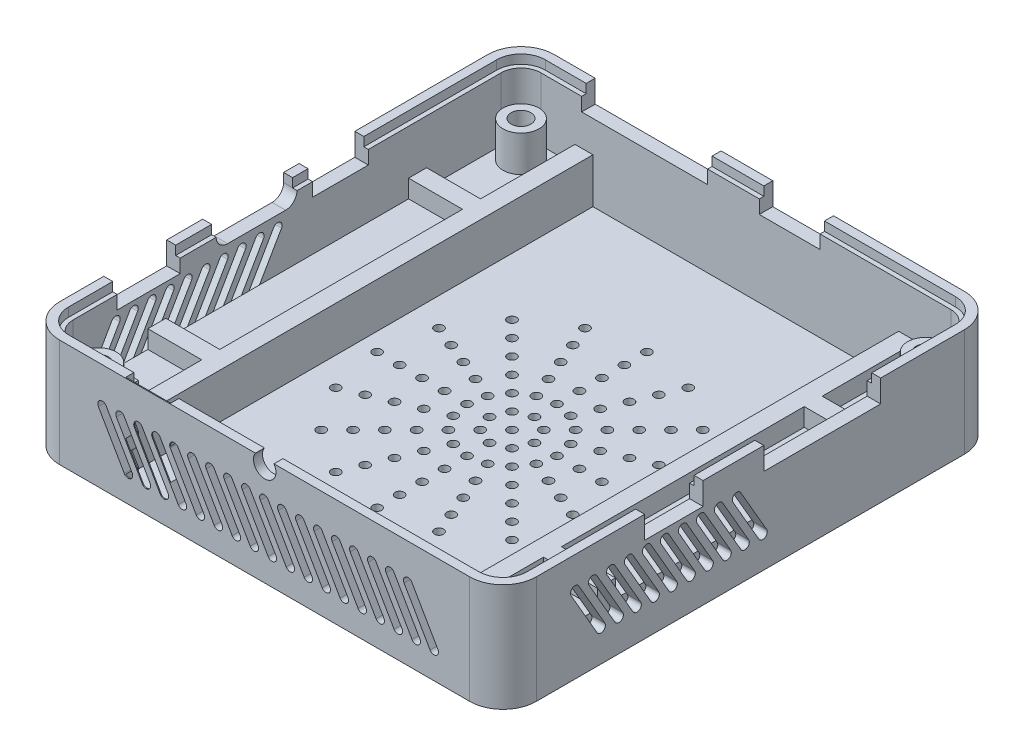
SolidWorks part; units mm, degrees
ref_plane "Front Plane" through (0, 0, 0) normal (0, 0, 1) x (1, 0, 0)
ref_plane "Top Plane" through (0, 0, 0) normal (0, 1, 0) x (1, 0, 0)
ref_plane "Right Plane" through (0, 0, 0) normal (1, 0, 0) x (0, 0, -1)
sketch "Sketch1" plane through (0, 0, 0) normal (0, 1, 0) x (1, 0, 0)
  line L5 (-25.5, 23.8) -> (-25.5, -23.8)
  line L6 (-22.8, 26) -> (22.8, 26)
  line L18 (-25, 23.8) -> (-25, -23.8)
  line L19 (-22.8, -26) -> (22.8, -26)
  line L20 (25, 23.8) -> (25, -23.8)
  line L21 (-25, 26) -> (25, -26) construction
  line L22 (-25, -26) -> (25, 26) construction
  line L23 (-22.8, -26.5) -> (22.8, -26.5)
  line L24 (25.5, 23.8) -> (25.5, -23.8)
  line L25 (-22.8, 26.5) -> (22.8, 26.5)
  line L26 (-26.5, 23.8) -> (-26.5, -23.8)
  line L27 (-22.8, -27.5) -> (22.8, -27.5)
  line L28 (26.5, 23.8) -> (26.5, -23.8)
  line L29 (-22.8, 27.5) -> (22.8, 27.5)
  line L30 (-19, 13.5) -> (-19, -13.5)
  line L31 (-19, 26) -> (-17, 26)
  line L32 (-19, 26) -> (-19, 15.5)
  line L33 (-19, -26) -> (-17, -26)
  line L34 (-17, 26) -> (-17, -26)
  line L35 (17, -26) -> (19, -26)
  line L36 (17, -26) -> (17, 26)
  line L37 (17, 26) -> (19, 26)
  line L38 (19, -26) -> (19, -15.5)
  line L39 (-25, 15.5) -> (-19, 15.5)
  line L40 (-25, 15.5) -> (-25, 13.5)
  line L41 (-25, 13.5) -> (-19, 13.5)
  line L43 (-25, -13.5) -> (-19, -13.5)
  line L44 (-25, -13.5) -> (-25, -15.5)
  line L45 (-25, -15.5) -> (-19, -15.5)
  line L47 (19, 15.5) -> (25, 15.5)
  line L48 (17, 15.5) -> (17, 13.5)
  line L49 (19, 13.5) -> (25, 13.5)
  line L50 (25, 15.5) -> (25, 13.5)
  line L51 (19, -13.5) -> (25, -13.5)
  line L52 (17, -13.5) -> (17, -15.5)
  line L53 (19, -15.5) -> (25, -15.5)
  line L54 (25, -13.5) -> (25, -15.5)
  line L55 (19, 15.5) -> (19, 26)
  line L56 (19, -13.5) -> (19, 13.5)
  line L57 (-19, -15.5) -> (-19, -26)
  circle A20 centre (-22.5, 23.5) radius 1.1
  circle A21 centre (22.5, 23.5) radius 1.1
  circle A22 centre (-22.5, -23.5) radius 1.1
  circle A23 centre (22.5, -23.5) radius 1.1
  circle A24 centre (-22.5, 23.5) radius 2
  circle A25 centre (22.5, 23.5) radius 2
  circle A26 centre (22.5, -23.5) radius 2
  circle A27 centre (-22.5, -23.5) radius 2
  arc A28 (-22.8, -26) -> (-25, -23.8) centre (-22.8, -23.8) cw
  arc A29 (25, -23.8) -> (22.8, -26) centre (22.8, -23.8) cw
  arc A30 (25, 23.8) -> (22.8, 26) centre (22.8, 23.8) ccw
  arc A31 (-22.8, 26) -> (-25, 23.8) centre (-22.8, 23.8) ccw
  arc A32 (-22.8, -26.5) -> (-25.5, -23.8) centre (-22.8, -23.8) cw
  arc A33 (25.5, -23.8) -> (22.8, -26.5) centre (22.8, -23.8) cw
  arc A34 (25.5, 23.8) -> (22.8, 26.5) centre (22.8, 23.8) ccw
  arc A35 (-22.8, 26.5) -> (-25.5, 23.8) centre (-22.8, 23.8) ccw
  arc A36 (-22.8, -27.5) -> (-26.5, -23.8) centre (-22.8, -23.8) cw
  arc A37 (26.5, -23.8) -> (22.8, -27.5) centre (22.8, -23.8) cw
  arc A38 (26.5, 23.8) -> (22.8, 27.5) centre (22.8, 23.8) ccw
  arc A39 (-22.8, 27.5) -> (-26.5, 23.8) centre (-22.8, 23.8) ccw
  point P0 (0, 0)
  dimension "D3" = 2.2
  dimension "D6" = 2.2
  dimension "D7" = 2.5
  dimension "D8" = 2.5
  dimension "D9" = 2.5
  dimension "D10" = 2.5
  dimension "D11" = 2.5
  dimension "D12" = 2.5
  dimension "D13" = 2.5
  dimension "D14" = 2.5
  dimension "D15" = 4
  dimension "D16" = 4
  dimension "D17" = 4
  dimension "D18" = 4
  dimension "D19" = 2.2
  dimension "D20" = 0.5
  dimension "D4" = 2.2
  dimension "D5" = 2.2
  dimension "D1" = 52
  dimension "D2" = 50
  dimension "D22" = 53
  dimension "D23" = 36
  dimension "D24" = 2
  dimension "D25" = 2
  dimension "D26" = 6
  dimension "D27" = 6
  dimension "D28" = 2
  dimension "D29" = 8
  dimension "D30" = 2
  dimension "D31" = 8
  dimension "D32" = 2
  dimension "D33" = 8
  dimension "D34" = 2
  dimension "D35" = 8
  dimension "D21" = 1.5
extrude "Boss-Extrude1" add sketch "Sketch1" along normal blind 12 contours L29 A39 L26 A36 L27 A37 L28 A38 A35 L25 A34 L24 A33 L23 A32 L5 region at (-24.8762, 0, -25.8762)
extrude "Boss-Extrude2" add sketch "Sketch1<10>" along normal blind 11 contours L25 A35 L5 A32 L23 A33 L24 A34 A31 L6 A30 L20 A29 L19 A28 L18 region at (-24.6572, 0, -25.6572)
sketch "Sketch1<10>" plane through (0, 0, 0) normal (0, 1, 0) x (1, 0, 0) same geometry as "Sketch1"
extrude "Boss-Extrude3" add sketch "Sketch1<11>" along normal blind 8 separate body contours A24 A20 | A27 A22 | A26 A23 | A25 A21 region at (-24.4434, 0, -23.5) region at (20.5566, 0, -23.5) region at (20.5566, 0, 23.5) region at (-24.4434, 0, 23.5)
sketch "Sketch1<11>" plane through (0, 0, 0) normal (0, 1, 0) x (1, 0, 0) same geometry as "Sketch1"
extrude "Boss-Extrude4" add sketch "Sketch1<12>" along normal blind 4 contours L18 L43 L30 L41 | L6 A31 L18 L39 L32 A24 | L19 L36 L6 L34 | A28 L19 L57 L45 L18 A27 | A29 L20 L53 L38 L19 A26 | L56 L51 L20 L49 | L20 A30 L6 L55 L47 A25 region at (-21.82, 0, -19.9503) region at (0, 0, 0) region at (-22, 0, 0) region at (21.82, 0, -19.9503) region at (-21.82, 0, 19.9503) region at (21.82, 0, 19.9503) region at (22, 0, 0)
sketch "Sketch1<12>" plane through (0, 0, 0) normal (0, 1, 0) x (1, 0, 0) same geometry as "Sketch1"
extrude "Boss-Extrude5" add sketch "Sketch1<13>" along normal blind 6 contours L45 L57 L19 L34 L6 L32 L39 L18 L41 L30 L43 | L51 L56 L49 L20 L47 L55 L6 L36 L19 L38 L53 region at (-18.75, 0, 0) region at (18.75, 0, 0)
sketch "Sketch1<13>" plane through (0, 0, 0) normal (0, 1, 0) x (1, 0, 0) same geometry as "Sketch1"
sketch "Sketch2" plane through (0, 4, 0) normal (0, 1, 0) x (1, 0, 0)
  line L1 (-17, 26) -> (17, 26)
  line L2 (-17, 26) -> (-17, -26)
  line L3 (-17, -26) -> (17, -26)
  line L4 (17, 26) -> (17, -26)
  line L5 (-17, 26) -> (17, -26) construction
  line L6 (-17, -26) -> (17, 26) construction
  point P0 (0, 0)
extrude "Cut-Extrude1" cut sketch "Sketch2" against normal blind 3
sketch "Sketch3" plane through (0, 0, 0) normal (0, -1, 0) x (1, 0, 0)
  circle A0 centre (-22.5, 23.5) radius 2
  circle A1 centre (22.5, 23.5) radius 2
  circle A2 centre (-22.5, -23.5) radius 2
  circle A3 centre (22.5, -23.5) radius 2
  circle A4 centre (0, 12.5) radius 0.5
  circle A5 centre (4.7835, 11.5485) radius 0.5
  circle A6 centre (8.8388, 8.8388) radius 0.5
  circle A7 centre (11.5485, 4.7835) radius 0.5
  circle A8 centre (12.5, 0) radius 0.5
  circle A9 centre (11.5485, -4.7835) radius 0.5
  circle A10 centre (8.8388, -8.8388) radius 0.5
  circle A11 centre (4.7835, -11.5485) radius 0.5
  circle A12 centre (0, -12.5) radius 0.5
  circle A13 centre (-4.7835, -11.5485) radius 0.5
  circle A14 centre (-8.8388, -8.8388) radius 0.5
  circle A15 centre (-11.5485, -4.7835) radius 0.5
  circle A16 centre (-12.5, 0) radius 0.5
  circle A17 centre (-11.5485, 4.7835) radius 0.5
  circle A18 centre (-8.8388, 8.8388) radius 0.5
  circle A19 centre (-4.7835, 11.5485) radius 0.5
  circle A20 centre (0, 10) radius 0.5
  circle A21 centre (0, 7.5) radius 0.5
  circle A22 centre (0, 5) radius 0.5
  circle A23 centre (0, 2.5) radius 0.5
  circle A24 centre (0, 0) radius 0.5
  circle A25 centre (3.8268, 9.2388) radius 0.5
  circle A26 centre (7.0711, 7.0711) radius 0.5
  circle A27 centre (9.2388, 3.8268) radius 0.5
  circle A28 centre (10, 0) radius 0.5
  circle A29 centre (9.2388, -3.8268) radius 0.5
  circle A30 centre (7.0711, -7.0711) radius 0.5
  circle A31 centre (3.8268, -9.2388) radius 0.5
  circle A32 centre (0, -10) radius 0.5
  circle A33 centre (-3.8268, -9.2388) radius 0.5
  circle A34 centre (-7.0711, -7.0711) radius 0.5
  circle A35 centre (-9.2388, -3.8268) radius 0.5
  circle A36 centre (-10, 0) radius 0.5
  circle A37 centre (-9.2388, 3.8268) radius 0.5
  circle A38 centre (-7.0711, 7.0711) radius 0.5
  circle A39 centre (-3.8268, 9.2388) radius 0.5
  circle A40 centre (2.8701, 6.9291) radius 0.5
  circle A41 centre (5.3033, 5.3033) radius 0.5
  circle A42 centre (6.9291, 2.8701) radius 0.5
  circle A43 centre (7.5, 0) radius 0.5
  circle A44 centre (6.9291, -2.8701) radius 0.5
  circle A45 centre (5.3033, -5.3033) radius 0.5
  circle A46 centre (2.8701, -6.9291) radius 0.5
  circle A47 centre (0, -7.5) radius 0.5
  circle A48 centre (-2.8701, -6.9291) radius 0.5
  circle A49 centre (-5.3033, -5.3033) radius 0.5
  circle A50 centre (-6.9291, -2.8701) radius 0.5
  circle A51 centre (-7.5, 0) radius 0.5
  circle A52 centre (-6.9291, 2.8701) radius 0.5
  circle A53 centre (-5.3033, 5.3033) radius 0.5
  circle A54 centre (-2.8701, 6.9291) radius 0.5
  circle A55 centre (1.9134, 4.6194) radius 0.5
  circle A56 centre (3.5355, 3.5355) radius 0.5
  circle A57 centre (4.6194, 1.9134) radius 0.5
  circle A58 centre (5, 0) radius 0.5
  circle A59 centre (4.6194, -1.9134) radius 0.5
  circle A60 centre (3.5355, -3.5355) radius 0.5
  circle A61 centre (1.9134, -4.6194) radius 0.5
  circle A62 centre (0, -5) radius 0.5
  circle A63 centre (-1.9134, -4.6194) radius 0.5
  circle A64 centre (-3.5355, -3.5355) radius 0.5
  circle A65 centre (-4.6194, -1.9134) radius 0.5
  circle A66 centre (-5, 0) radius 0.5
  circle A67 centre (-4.6194, 1.9134) radius 0.5
  circle A68 centre (-3.5355, 3.5355) radius 0.5
  circle A69 centre (-1.9134, 4.6194) radius 0.5
  circle A70 centre (1.7678, 1.7678) radius 0.5
  circle A71 centre (2.5, 0) radius 0.5
  circle A72 centre (1.7678, -1.7678) radius 0.5
  circle A73 centre (0, -2.5) radius 0.5
  circle A74 centre (-1.7678, -1.7678) radius 0.5
  circle A75 centre (-2.5, 0) radius 0.5
  circle A76 centre (-1.7678, 1.7678) radius 0.5
  circle A78 centre (0, 15) radius 0.5
  circle A82 centre (5.7403, 13.8582) radius 0.5
  circle A83 centre (10.6066, 10.6066) radius 0.5
  circle A84 centre (13.8582, 5.7403) radius 0.5
  circle A85 centre (15, 0) radius 0.5
  circle A86 centre (13.8582, -5.7403) radius 0.5
  circle A87 centre (10.6066, -10.6066) radius 0.5
  circle A88 centre (5.7403, -13.8582) radius 0.5
  circle A89 centre (0, -15) radius 0.5
  circle A90 centre (-5.7403, -13.8582) radius 0.5
  circle A91 centre (-10.6066, -10.6066) radius 0.5
  circle A92 centre (-13.8582, -5.7403) radius 0.5
  circle A93 centre (-15, 0) radius 0.5
  circle A94 centre (-13.8582, 5.7403) radius 0.5
  circle A95 centre (-10.6066, 10.6066) radius 0.5
  circle A96 centre (-5.7403, 13.8582) radius 0.5
  circle A97 centre (0, 17.5) radius 0.5 [skipped]
  circle A98 centre (0, 20) radius 0.5 [skipped]
  circle A99 centre (0, 22.5) radius 0.5 [skipped]
  point P49 (0, 0)
  point P85 (0, 0)
  point P116 (0, 0)
  point P148 (0, 0)
  point P162 (0, 0)
  point P204 (0, 0)
  dimension "D1" = 2.5
  dimension "D6" = 5
  dimension "D7" = 16
  dimension "D2" = 2.5
  dimension "D3" = 2.5
  dimension "D4" = 2.5
  dimension "D5" = 2.5
extrude "Cut-Extrude2" cut sketch "Sketch3" against normal blind 4
sketch "Sketch4" plane through (0, 0, -27.5) normal (0, 0, -1) x (-1, 0, 0)
  line L8 (22.8, 12) -> (-22.8, 12) construction
  line L9 (18.25, 12) -> (4.25, 12)
  line L10 (18.25, 12) -> (18.25, 9.5)
  line L11 (18.25, 9.5) -> (4.25, 9.5)
  line L12 (4.25, 12) -> (4.25, 9.5)
  line L13 (26.5, 12) -> (26.5, 0) construction
  line L14 (-8.25, 12) -> (-1.5, 12)
  line L15 (-8.25, 12) -> (-8.25, 9.5)
  line L16 (-8.25, 9.5) -> (-1.5, 9.5)
  line L17 (-1.5, 12) -> (-1.5, 9.5)
  dimension "D1" = 2.5
  dimension "D2" = 14
  dimension "D3" = 8.25
  dimension "D4" = 5.75
  dimension "D5" = 6.75
  dimension "D6" = 2.5
extrude "Cut-Extrude3" cut sketch "Sketch4" against normal blind 4
sketch "Sketch5" plane through (-26.5, 0, 0) normal (-1, 0, 0) x (0, 0, 1)
  line L0 (-23.8, 12) -> (23.8, 12) construction
  line L1 (-9.02, 12) -> (-2.82, 12)
  line L2 (-9.02, 12) -> (-9.02, 9.5)
  line L3 (-9.02, 9.5) -> (-2.82, 9.5)
  line L4 (-2.82, 12) -> (-2.82, 9.5)
  line L6 (-1.1, 12) -> (7.9, 12)
  line L7 (-1.1, 12) -> (-1.1, 11.03)
  line L8 (0.18, 9.75) -> (6.62, 9.75)
  line L9 (7.9, 12) -> (7.9, 11.03)
  line L10 (-27.5, 12) -> (-27.5, 0) construction
  line L11 (11.9, 12) -> (18.9, 12)
  line L12 (11.9, 12) -> (11.9, 9.5)
  line L13 (11.9, 9.5) -> (18.9, 9.5)
  line L14 (18.9, 12) -> (18.9, 9.5)
  arc A0 (7.9, 11.03) -> (6.62, 9.75) centre (6.62, 11.03) cw
  arc A1 (0.18, 9.75) -> (-1.1, 11.03) centre (0.18, 11.03) cw
  point P14 (7.9, 9.75)
  point P17 (-1.1, 9.75)
  dimension "D7" = 1.28
  dimension "D2" = 2.5
  dimension "D3" = 6.2
  dimension "D4" = 1.72
  dimension "D5" = 9
  dimension "D6" = 2.25
  dimension "D8" = 4
  dimension "D9" = 7
  dimension "D10" = 2.5
  dimension "D11" = 18.48
extrude "Cut-Extrude4" cut sketch "Sketch5" against normal blind 4
sketch "Sketch6" plane through (0, 0, 26) normal (0, 0, -1) x (-1, 0, 0)
  line L7 (22.8, 12) -> (-22.8, 12) construction
  line L8 (10.55, 12) -> (15.55, 12)
  line L9 (10.55, 12) -> (10.55, 1)
  line L10 (10.55, 1) -> (15.55, 1)
  line L11 (15.55, 12) -> (15.55, 1)
  line L12 (22.8, 12) -> (22.8, 0) construction
  line L13 (22.8, 0) -> (-22.8, 0) construction
  dimension "D1" = 7.25
  dimension "D2" = 5
  dimension "D3" = 11
  dimension "D4" = 1
extrude "Cut-Extrude5" cut sketch "Sketch6" against normal blind 1
sketch "Sketch7" plane through (26.5, 0, 0) normal (1, 0, 0) x (0, 0, -1)
  line L0 (23.8, 12) -> (-23.8, 12) construction
  line L1 (1.5, 12) -> (14.5, 12)
  line L2 (1.5, 12) -> (1.5, 9.5)
  line L3 (1.5, 9.5) -> (14.5, 9.5)
  line L4 (14.5, 12) -> (14.5, 9.5)
  line L5 (27.5, 12) -> (27.5, 0) construction
  line L7 (-11.75, 12) -> (-5.25, 12)
  line L8 (-11.75, 12) -> (-11.75, 9.5)
  line L9 (-11.75, 9.5) -> (-5.25, 9.5)
  line L10 (-5.25, 12) -> (-5.25, 9.5)
  dimension "D1" = 13
  dimension "D2" = 2.5
  dimension "D3" = 13
  dimension "D4" = 6.75
  dimension "D5" = 6.5
  dimension "D6" = 2.5
extrude "Cut-Extrude6" cut sketch "Sketch7" against normal blind 5
sketch "Sketch9" plane through (0, 0, 27.5) normal (0, 0, 1) x (1, 0, 0)
  line L0 (-22.8, 12) -> (22.8, 12) construction
  line L1 (-26.5, 12) -> (-26.5, 0) construction
  circle A0 centre (0, 11.29) radius 1.25
  dimension "D1" = 0.71
  dimension "D2" = 2.5
  dimension "D3" = 26.5
extrude "Cut-Extrude8" cut sketch "Sketch9" against normal blind 5
sketch "Sketch10" plane through (26.5, 0, 0) normal (1, 0, 0) x (0, 0, -1)
  line L0 (-19.067, 8.75) -> (-16.1802, 3.75)
  line L1 (-19.933, 8.25) -> (-17.0463, 3.25)
  line L2 (-27.5, 12) -> (-27.5, 0) construction
  line L3 (1.5, 12) -> (-5.25, 12) construction
  line L4 (23.8, 0) -> (-23.8, 0) construction
  line L5 (-17.067, 8.75) -> (-14.1802, 3.75)
  line L6 (-17.933, 8.25) -> (-15.0463, 3.25)
  line L7 (-15.067, 8.75) -> (-12.1802, 3.75)
  line L8 (-15.933, 8.25) -> (-13.0463, 3.25)
  line L9 (-13.067, 8.75) -> (-10.1802, 3.75)
  line L10 (-13.933, 8.25) -> (-11.0463, 3.25)
  line L11 (-11.067, 8.75) -> (-8.1802, 3.75)
  line L12 (-11.933, 8.25) -> (-9.0463, 3.25)
  line L13 (-9.067, 8.75) -> (-6.1802, 3.75)
  line L14 (-9.933, 8.25) -> (-7.0463, 3.25)
  line L15 (-7.067, 8.75) -> (-4.1802, 3.75)
  line L16 (-7.933, 8.25) -> (-5.0463, 3.25)
  line L17 (-5.067, 8.75) -> (-2.1802, 3.75)
  line L18 (-5.933, 8.25) -> (-3.0463, 3.25)
  line L19 (-3.067, 8.75) -> (-0.1802, 3.75)
  line L20 (-3.933, 8.25) -> (-1.0463, 3.25)
  line L21 (-1.067, 8.75) -> (1.8198, 3.75)
  line L22 (-1.933, 8.25) -> (0.9537, 3.25)
  arc A0 (-19.933, 8.25) -> (-19.067, 8.75) centre (-19.5, 8.5) cw
  arc A1 (-17.0463, 3.25) -> (-16.1802, 3.75) centre (-16.6132, 3.5) ccw
  arc A2 (-17.933, 8.25) -> (-17.067, 8.75) centre (-17.5, 8.5) cw
  arc A3 (-15.0463, 3.25) -> (-14.1802, 3.75) centre (-14.6132, 3.5) ccw
  arc A4 (-15.933, 8.25) -> (-15.067, 8.75) centre (-15.5, 8.5) cw
  arc A5 (-13.0463, 3.25) -> (-12.1802, 3.75) centre (-12.6132, 3.5) ccw
  arc A6 (-13.933, 8.25) -> (-13.067, 8.75) centre (-13.5, 8.5) cw
  arc A7 (-11.0463, 3.25) -> (-10.1802, 3.75) centre (-10.6132, 3.5) ccw
  arc A8 (-11.933, 8.25) -> (-11.067, 8.75) centre (-11.5, 8.5) cw
  arc A9 (-9.0463, 3.25) -> (-8.1802, 3.75) centre (-8.6132, 3.5) ccw
  arc A10 (-9.933, 8.25) -> (-9.067, 8.75) centre (-9.5, 8.5) cw
  arc A11 (-7.0463, 3.25) -> (-6.1802, 3.75) centre (-6.6132, 3.5) ccw
  arc A12 (-5.0463, 3.25) -> (-4.1802, 3.75) centre (-4.6132, 3.5) ccw
  arc A13 (-7.933, 8.25) -> (-7.067, 8.75) centre (-7.5, 8.5) cw
  arc A14 (-3.0463, 3.25) -> (-2.1802, 3.75) centre (-2.6132, 3.5) ccw
  arc A15 (-5.933, 8.25) -> (-5.067, 8.75) centre (-5.5, 8.5) cw
  arc A16 (-1.0463, 3.25) -> (-0.1802, 3.75) centre (-0.6132, 3.5) ccw
  arc A17 (-3.933, 8.25) -> (-3.067, 8.75) centre (-3.5, 8.5) cw
  arc A18 (0.9537, 3.25) -> (1.8198, 3.75) centre (1.3868, 3.5) ccw
  arc A19 (-1.933, 8.25) -> (-1.067, 8.75) centre (-1.5, 8.5) cw
  dimension "D5" = 3.5
  dimension "D6" = 3.5
  dimension "D7" = 8
  dimension "D1" = 1
  dimension "D2" = 5
  dimension "D3" = 60
  dimension "D4" = 30
  dimension "D10" = 2
  dimension "D8" = 6
  dimension "D9" = 4
extrude "Cut-Extrude9" cut sketch "Sketch10" against normal blind 1.5
sketch "Sketch12" plane through (0, 0, 26) normal (0, 0, -1) x (-1, 0, 0)
  line L0 (22.8, 12) -> (15.55, 12) construction
  line L1 (-1.0288, 12) -> (-22.8, 12) construction
  circle A0 centre (-2.5, 11.5) radius 0.25
  circle A1 centre (2.5, 11.5) radius 0.25
  arc A2 (-1.0288, 12) -> (-1.2159, 11) centre (0, 11.29) ccw construction
  arc A3 (1.2159, 11) -> (1.0288, 12) centre (0, 11.29) ccw construction
  dimension "D1" = 0.5
  dimension "D2" = 0.5
  dimension "D3" = 2.5
  dimension "D4" = 2.5
  dimension "D5" = 0.5
  dimension "D6" = 0.5
  dimension "D7" = 5
extrude "Cut-Extrude12" cut sketch "Sketch12" against normal blind 1 contours A1 | A0
sketch "Sketch13" plane through (0, 0, 26) normal (0, 0, -1) x (-1, 0, 0)
  line L0 (-1.2755, 11) -> (-1.2755, 11.29)
  line L1 (-1.2159, 11) -> (-22.8, 11) construction
  line L2 (-1.2755, 11.29) -> (0.4692, 11.29)
  circle A0 centre (0, 11.29) radius 2
extrude "Cut-Extrude13" cut sketch "Sketch13" against normal blind 0.5 contours A0
sketch "Sketch14" plane through (0, 0, 27.5) normal (0, 0, 1) x (1, 0, 0)
  line L0 (-17.634, 8.25) -> (-14.7472, 3.25)
  line L1 (-18.5, 7.75) -> (-15.6132, 2.75)
  line L2 (-22.8, 12) -> (-1.0288, 12) construction
  line L5 (-15.634, 8.25) -> (-12.7472, 3.25)
  line L6 (-16.5, 7.75) -> (-13.6132, 2.75)
  line L7 (-13.634, 8.25) -> (-10.7472, 3.25)
  line L8 (-14.5, 7.75) -> (-11.6132, 2.75)
  line L9 (-11.634, 8.25) -> (-8.7472, 3.25)
  line L10 (-12.5, 7.75) -> (-9.6132, 2.75)
  line L11 (-9.634, 8.25) -> (-6.7472, 3.25)
  line L12 (-10.5, 7.75) -> (-7.6132, 2.75)
  line L13 (-7.634, 8.25) -> (-4.7472, 3.25)
  line L14 (-8.5, 7.75) -> (-5.6132, 2.75)
  line L15 (-5.634, 8.25) -> (-2.7472, 3.25)
  line L16 (-6.5, 7.75) -> (-3.6132, 2.75)
  line L17 (-3.634, 8.25) -> (-0.7472, 3.25)
  line L18 (-4.5, 7.75) -> (-1.6132, 2.75)
  line L19 (-1.634, 8.25) -> (1.2528, 3.25)
  line L20 (-2.5, 7.75) -> (0.3868, 2.75)
  line L21 (0.366, 8.25) -> (3.2528, 3.25)
  line L22 (-0.5, 7.75) -> (2.3868, 2.75)
  line L23 (2.366, 8.25) -> (5.2528, 3.25)
  line L24 (1.5, 7.75) -> (4.3868, 2.75)
  line L25 (4.366, 8.25) -> (7.2528, 3.25)
  line L26 (3.5, 7.75) -> (6.3868, 2.75)
  line L27 (6.366, 8.25) -> (9.2528, 3.25)
  line L28 (5.5, 7.75) -> (8.3868, 2.75)
  line L29 (8.366, 8.25) -> (11.2528, 3.25)
  line L30 (7.5, 7.75) -> (10.3868, 2.75)
  line L31 (10.366, 8.25) -> (13.2528, 3.25)
  line L32 (9.5, 7.75) -> (12.3868, 2.75)
  line L33 (12.366, 8.25) -> (15.2528, 3.25)
  line L34 (11.5, 7.75) -> (14.3868, 2.75)
  line L35 (14.366, 8.25) -> (17.2528, 3.25)
  line L36 (13.5, 7.75) -> (16.3868, 2.75)
  line L37 (16.366, 8.25) -> (19.2528, 3.25)
  line L38 (15.5, 7.75) -> (18.3868, 2.75)
  arc A0 (-18.5, 7.75) -> (-17.634, 8.25) centre (-18.067, 8) cw
  arc A1 (-15.6132, 2.75) -> (-14.7472, 3.25) centre (-15.1802, 3) ccw
  arc A2 (-13.6132, 2.75) -> (-12.7472, 3.25) centre (-13.1802, 3) ccw
  arc A3 (-16.5, 7.75) -> (-15.634, 8.25) centre (-16.067, 8) cw
  arc A4 (-11.6132, 2.75) -> (-10.7472, 3.25) centre (-11.1802, 3) ccw
  arc A5 (-14.5, 7.75) -> (-13.634, 8.25) centre (-14.067, 8) cw
  arc A6 (-9.6132, 2.75) -> (-8.7472, 3.25) centre (-9.1802, 3) ccw
  arc A7 (-12.5, 7.75) -> (-11.634, 8.25) centre (-12.067, 8) cw
  arc A8 (-7.6132, 2.75) -> (-6.7472, 3.25) centre (-7.1802, 3) ccw
  arc A9 (-10.5, 7.75) -> (-9.634, 8.25) centre (-10.067, 8) cw
  arc A10 (-5.6132, 2.75) -> (-4.7472, 3.25) centre (-5.1802, 3) ccw
  arc A11 (-8.5, 7.75) -> (-7.634, 8.25) centre (-8.067, 8) cw
  arc A12 (-3.6132, 2.75) -> (-2.7472, 3.25) centre (-3.1802, 3) ccw
  arc A13 (-6.5, 7.75) -> (-5.634, 8.25) centre (-6.067, 8) cw
  arc A14 (-1.6132, 2.75) -> (-0.7472, 3.25) centre (-1.1802, 3) ccw
  arc A15 (-4.5, 7.75) -> (-3.634, 8.25) centre (-4.067, 8) cw
  arc A16 (0.3868, 2.75) -> (1.2528, 3.25) centre (0.8198, 3) ccw
  arc A17 (-2.5, 7.75) -> (-1.634, 8.25) centre (-2.067, 8) cw
  arc A18 (2.3868, 2.75) -> (3.2528, 3.25) centre (2.8198, 3) ccw
  arc A19 (-0.5, 7.75) -> (0.366, 8.25) centre (-0.067, 8) cw
  arc A20 (4.3868, 2.75) -> (5.2528, 3.25) centre (4.8198, 3) ccw
  arc A21 (1.5, 7.75) -> (2.366, 8.25) centre (1.933, 8) cw
  arc A22 (6.3868, 2.75) -> (7.2528, 3.25) centre (6.8198, 3) ccw
  arc A23 (3.5, 7.75) -> (4.366, 8.25) centre (3.933, 8) cw
  arc A24 (8.3868, 2.75) -> (9.2528, 3.25) centre (8.8198, 3) ccw
  arc A25 (5.5, 7.75) -> (6.366, 8.25) centre (5.933, 8) cw
  arc A26 (10.3868, 2.75) -> (11.2528, 3.25) centre (10.8198, 3) ccw
  arc A27 (7.5, 7.75) -> (8.366, 8.25) centre (7.933, 8) cw
  arc A28 (12.3868, 2.75) -> (13.2528, 3.25) centre (12.8198, 3) ccw
  arc A29 (9.5, 7.75) -> (10.366, 8.25) centre (9.933, 8) cw
  arc A30 (14.3868, 2.75) -> (15.2528, 3.25) centre (14.8198, 3) ccw
  arc A31 (11.5, 7.75) -> (12.366, 8.25) centre (11.933, 8) cw
  arc A32 (16.3868, 2.75) -> (17.2528, 3.25) centre (16.8198, 3) ccw
  arc A33 (13.5, 7.75) -> (14.366, 8.25) centre (13.933, 8) cw
  arc A34 (18.3868, 2.75) -> (19.2528, 3.25) centre (18.8198, 3) ccw
  arc A35 (15.5, 7.75) -> (16.366, 8.25) centre (15.933, 8) cw
  dimension "D1" = 4
  dimension "D3" = 18
extrude "Cut-Extrude14" cut sketch "Sketch14" against normal blind 1.5
sketch "Sketch15" plane through (-26.5, 0, 0) normal (-1, 0, 0) x (0, 0, 1)
  line L16 (19.5, 8.75) -> (22.3868, 3.75)
  line L17 (18.634, 8.25) -> (21.5207, 3.25)
  line L21 (18.9, 12) -> (23.8, 12) construction
  line L22 (27.5, 12) -> (27.5, 0) construction
  line L23 (-23.8, 0) -> (23.8, 0) construction
  line L24 (17.5, 8.75) -> (20.3868, 3.75)
  line L25 (16.634, 8.25) -> (19.5207, 3.25)
  line L26 (15.5, 8.75) -> (18.3868, 3.75)
  line L27 (14.634, 8.25) -> (17.5207, 3.25)
  line L28 (13.5, 8.75) -> (16.3868, 3.75)
  line L29 (12.634, 8.25) -> (15.5207, 3.25)
  line L30 (11.5, 8.75) -> (14.3868, 3.75)
  line L31 (10.634, 8.25) -> (13.5207, 3.25)
  line L32 (9.5, 8.75) -> (12.3868, 3.75)
  line L33 (8.634, 8.25) -> (11.5207, 3.25)
  line L34 (7.5, 8.75) -> (10.3868, 3.75)
  line L35 (6.634, 8.25) -> (9.5207, 3.25)
  line L36 (5.5, 8.75) -> (8.3868, 3.75)
  line L37 (4.634, 8.25) -> (7.5207, 3.25)
  line L38 (3.5, 8.75) -> (6.3868, 3.75)
  line L39 (2.634, 8.25) -> (5.5207, 3.25)
  line L40 (1.5, 8.75) -> (4.3868, 3.75)
  line L41 (0.634, 8.25) -> (3.5207, 3.25)
  arc A16 (21.5207, 3.25) -> (22.3868, 3.75) centre (21.9537, 3.5) ccw
  arc A17 (18.634, 8.25) -> (19.5, 8.75) centre (19.067, 8.5) cw
  arc A18 (19.5207, 3.25) -> (20.3868, 3.75) centre (19.9537, 3.5) ccw
  arc A19 (16.634, 8.25) -> (17.5, 8.75) centre (17.067, 8.5) cw
  arc A20 (17.5207, 3.25) -> (18.3868, 3.75) centre (17.9537, 3.5) ccw
  arc A21 (14.634, 8.25) -> (15.5, 8.75) centre (15.067, 8.5) cw
  arc A22 (15.5207, 3.25) -> (16.3868, 3.75) centre (15.9537, 3.5) ccw
  arc A23 (12.634, 8.25) -> (13.5, 8.75) centre (13.067, 8.5) cw
  arc A24 (13.5207, 3.25) -> (14.3868, 3.75) centre (13.9537, 3.5) ccw
  arc A25 (10.634, 8.25) -> (11.5, 8.75) centre (11.067, 8.5) cw
  arc A26 (11.5207, 3.25) -> (12.3868, 3.75) centre (11.9537, 3.5) ccw
  arc A27 (8.634, 8.25) -> (9.5, 8.75) centre (9.067, 8.5) cw
  arc A28 (9.5207, 3.25) -> (10.3868, 3.75) centre (9.9537, 3.5) ccw
  arc A29 (6.634, 8.25) -> (7.5, 8.75) centre (7.067, 8.5) cw
  arc A30 (7.5207, 3.25) -> (8.3868, 3.75) centre (7.9537, 3.5) ccw
  arc A31 (4.634, 8.25) -> (5.5, 8.75) centre (5.067, 8.5) cw
  arc A32 (5.5207, 3.25) -> (6.3868, 3.75) centre (5.9537, 3.5) ccw
  arc A33 (2.634, 8.25) -> (3.5, 8.75) centre (3.067, 8.5) cw
  arc A34 (3.5207, 3.25) -> (4.3868, 3.75) centre (3.9537, 3.5) ccw
  arc A35 (0.634, 8.25) -> (1.5, 8.75) centre (1.067, 8.5) cw
  dimension "D2" = 8
  dimension "D3" = 3.5
  dimension "D1" = 3.5
  dimension "D6" = 5
  dimension "D9" = 2
  dimension "D4" = 10
  dimension "D5" = 1
  dimension "D7" = 30
  dimension "D8" = 0.7321
extrude "Cut-Extrude15" cut sketch "Sketch15" against normal blind 1.5
sketch "Sketch17" plane through (0, 12, 0) normal (0, 1, 0) x (1, 0, 0)
  line L0 (-15.55, -27) -> (-10.55, -27) construction
  line L1 (-15.55, -26.6) -> (-10.55, -26.6)
  line L2 (-15.55, -26.6) -> (-15.55, -27.4)
  line L3 (-15.55, -27.4) -> (-10.55, -27.4)
  line L4 (-10.55, -26.6) -> (-10.55, -27.4)
  line L5 (-15.55, -26.6) -> (-10.55, -27.4) construction
  line L6 (-15.55, -27.4) -> (-10.55, -26.6) construction
  point P0 (-13.05, -27)
  dimension "D1" = 0.8
  dimension "D2" = 5
extrude "Cut-Extrude16" cut sketch "Sketch17" against normal blind 11
